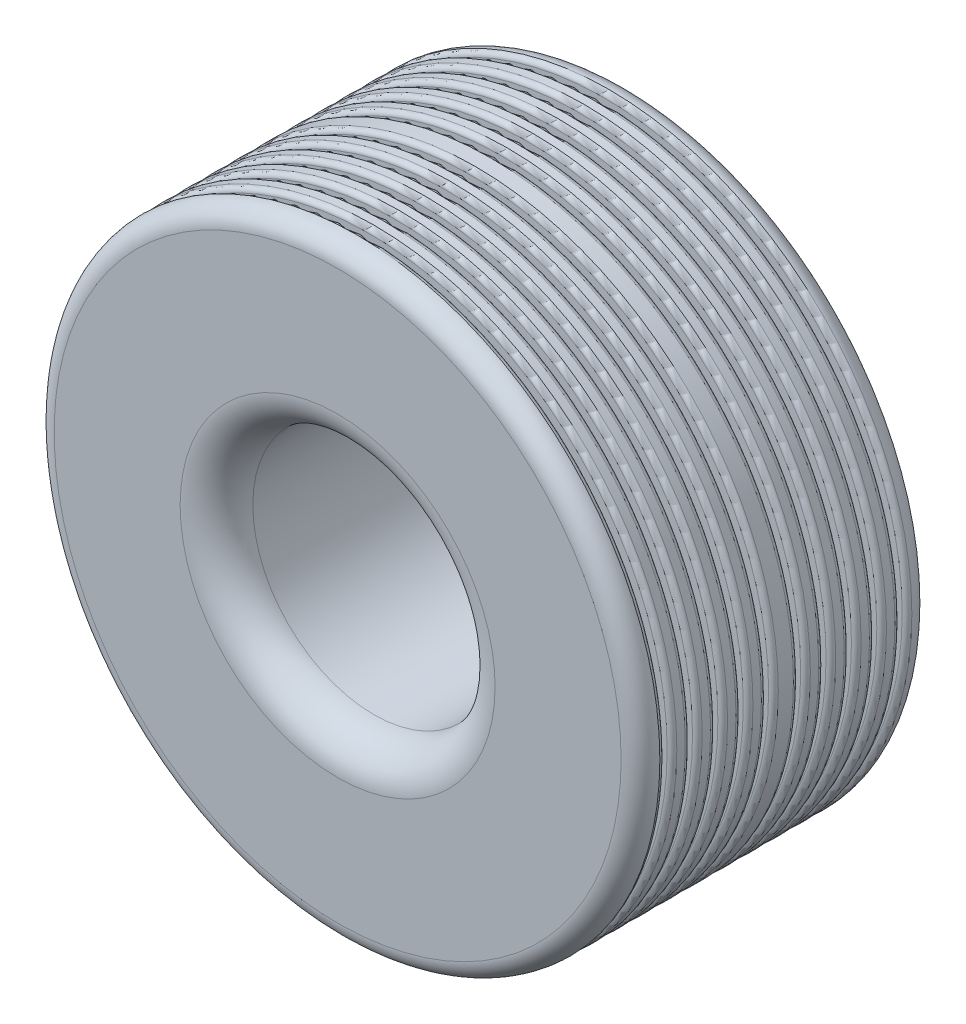
SolidWorks part; units mm, degrees
ref_plane "Front Plane" through (0, 0, 0) normal (0, 0, 1) x (1, 0, 0)
ref_plane "Top Plane" through (0, 0, 0) normal (0, 1, 0) x (1, 0, 0)
ref_plane "Right Plane" through (0, 0, 0) normal (1, 0, 0) x (0, 0, -1)
sketch "Sketch1" plane through (0, 0, 0) normal (0, 0, 1) x (1, 0, 0)
  circle A0 centre (0, 0) radius 125
  circle A1 centre (0, 0) radius 50
  dimension "D1" = 250
  dimension "D2" = 100
extrude "Boss-Extrude1" add sketch "Sketch1" along normal blind 120
sketch "Sketch5" plane through (0, 0, 0) normal (1, 0, 0) x (0, 0, -1)
  line L0 (0, 125) -> (-120, 125) construction
  line L1 (0, 0) -> (68.9161, 0) construction
  line L2 (-10, 94.315) -> (-10, 109.6769) construction
  line L3 (-110, 125) -> (-107, 125)
  line L4 (-110, 125) -> (-110, 95.8671)
  line L5 (-110, 95.8671) -> (-107, 95.8671)
  line L6 (-107, 125) -> (-107, 95.8671)
  line L7 (0, -125) -> (0, 125) construction
  line L8 (-10, 94.315) -> (-50, 94.315) construction
  line L9 (-99.5286, 95.8671) -> (-96.5286, 95.8671)
  line L10 (-96.5286, 125) -> (-96.5286, 95.8671)
  line L11 (-99.5286, 125) -> (-99.5286, 95.8671)
  line L12 (-99.5286, 125) -> (-96.5286, 125)
  line L13 (-89.0571, 95.8671) -> (-86.0571, 95.8671)
  line L14 (-86.0571, 125) -> (-86.0571, 95.8671)
  line L15 (-89.0571, 125) -> (-89.0571, 95.8671)
  line L16 (-89.0571, 125) -> (-86.0571, 125)
  line L17 (-78.5857, 95.8671) -> (-75.5857, 95.8671)
  line L18 (-75.5857, 125) -> (-75.5857, 95.8671)
  line L19 (-78.5857, 125) -> (-78.5857, 95.8671)
  line L20 (-78.5857, 125) -> (-75.5857, 125)
  line L21 (-68.1143, 95.8671) -> (-65.1143, 95.8671)
  line L22 (-65.1143, 125) -> (-65.1143, 95.8671)
  line L23 (-68.1143, 125) -> (-68.1143, 95.8671)
  line L24 (-68.1143, 125) -> (-65.1143, 125)
  line L25 (-60, 139.2594) -> (-60, 105.2826) construction
  line L26 (-51.8857, 125) -> (-54.8857, 125)
  line L27 (-51.8857, 125) -> (-51.8857, 95.8671)
  line L28 (-54.8857, 125) -> (-54.8857, 95.8671)
  line L29 (-51.8857, 95.8671) -> (-54.8857, 95.8671)
  line L30 (-41.4143, 125) -> (-44.4143, 125)
  line L31 (-41.4143, 125) -> (-41.4143, 95.8671)
  line L32 (-44.4143, 125) -> (-44.4143, 95.8671)
  line L33 (-41.4143, 95.8671) -> (-44.4143, 95.8671)
  line L34 (-30.9429, 125) -> (-33.9429, 125)
  line L35 (-30.9429, 125) -> (-30.9429, 95.8671)
  line L36 (-33.9429, 125) -> (-33.9429, 95.8671)
  line L37 (-30.9429, 95.8671) -> (-33.9429, 95.8671)
  line L38 (-20.4714, 125) -> (-23.4714, 125)
  line L39 (-20.4714, 125) -> (-20.4714, 95.8671)
  line L40 (-23.4714, 125) -> (-23.4714, 95.8671)
  line L41 (-20.4714, 95.8671) -> (-23.4714, 95.8671)
  line L42 (-13, 125) -> (-13, 95.8671)
  line L43 (-10, 95.8671) -> (-13, 95.8671)
  line L44 (-10, 125) -> (-10, 95.8671)
  line L45 (-10, 125) -> (-13, 125)
  dimension "D1" = 10
  dimension "D2" = 3
  dimension "D3" = 10
  dimension "D5" = 0
  dimension "D6" = 60
  dimension "D4" = 5
revolve "Cut-Revolve1" cut sketch "Sketch5" angle 360 about L1
fillet "Fillet1" radius 8 2 edges at (125, 0, 0) (125, 0, 120)
fillet "Fillet2" radius 15 2 edges at (50, 0, 0) (50, 0, 120)
fillet "Fillet3" radius 2 20 edges at (125, 0, 110) (125, 0, 10) (125, 0, 20.4714) (125, 0, 13) (125, 0, 30.9429) (125, 0, 23.4714) (125, 0, 41.4143) (125, 0, 33.9429) (125, 0, 51.8857) (125, 0, 44.4143) (125, 0, 65.1143) (125, 0, 54.8857) (125, 0, 75.5857) (125, 0, 68.1143) (125, 0, 86.0571) (125, 0, 78.5857) (125, 0, 96.5286) (125, 0, 89.0571) (125, 0, 107) (125, 0, 99.5286)
